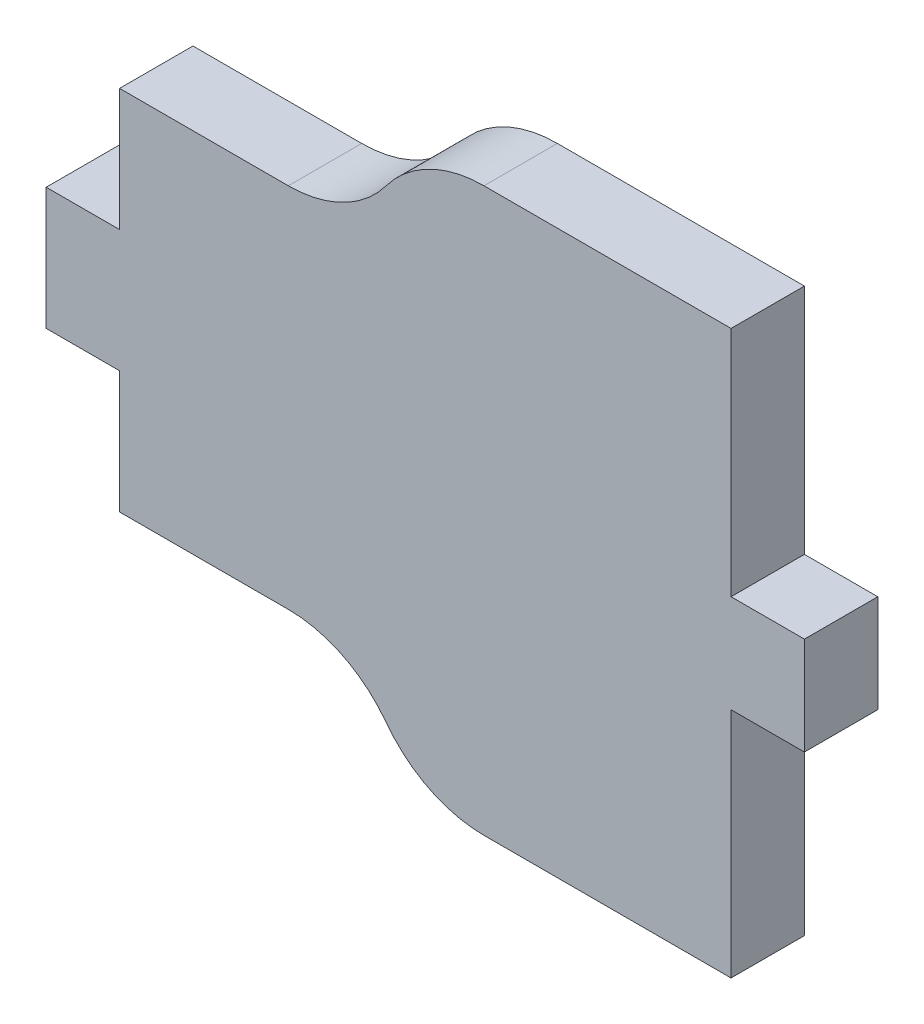
SolidWorks part; units mm, degrees
ref_plane "Plan de face" through (0, 0, 0) normal (0, 0, 1) x (1, 0, 0)
ref_plane "Plan de dessus" through (0, 0, 0) normal (0, 1, 0) x (1, 0, 0)
ref_plane "Plan de droite" through (0, 0, 0) normal (1, 0, 0) x (0, 0, -1)
sketch "Esquisse1" plane through (0, 0, 0) normal (0, 0, 1) x (1, 0, 0)
  line L1 (-22.2671, 18.0667) -> (27.7329, 18.0667)
  line L2 (-22.2671, 18.0667) -> (-22.2671, -11.9333)
  line L3 (-22.2671, -11.9333) -> (27.7329, -11.9333)
  line L4 (27.7329, 18.0667) -> (27.7329, -11.9333)
  dimension "D1" = 50
  dimension "D2" = 30
extrude "Boss.-Extru.1" add sketch "Esquisse1" along normal blind 6
sketch "Esquisse3" plane through (0, 0, 6) normal (0, 0, 1) x (1, 0, 0)
  line L0 (-2.2671, 18.0667) -> (-2.2671, -11.9333) construction
  line L1 (27.7329, 18.0667) -> (-22.2671, 18.0667) construction
  line L2 (-22.2671, -11.9333) -> (27.7329, -11.9333) construction
  line L3 (27.7329, -11.9333) -> (27.7329, 18.0667) construction
  line L5 (-2.2671, 18.0667) -> (27.7329, 18.0667)
  line L6 (-2.2671, 18.0667) -> (-2.2671, 26.0667)
  line L7 (-2.2671, 26.0667) -> (27.7329, 26.0667)
  line L8 (27.7329, 18.0667) -> (27.7329, 26.0667)
  line L9 (-2.2671, -11.9333) -> (27.7329, -11.9333)
  line L10 (-2.2671, -11.9333) -> (-2.2671, -19.9333)
  line L11 (-2.2671, -19.9333) -> (27.7329, -19.9333)
  line L12 (27.7329, -11.9333) -> (27.7329, -19.9333)
  dimension "D1" = 30
  dimension "D2" = 30
  dimension "D3" = 8
  dimension "D4" = 8
  dimension "D5" = 30
extrude "Boss.-Extru.2" add sketch "Esquisse3" against normal blind 6
fillet "Congé1" radius 10 1 edges at (-2.2671, 26.0667, 3)
fillet "Congé2" radius 10 1 edges at (-2.2671, -19.9333, 3)
fillet "Congé3" radius 10 1 edges
fillet "Congé4" radius 10 1 edges
sketch "Esquisse7" plane through (0, 0, 6) normal (0, 0, 1) x (1, 0, 0)
  line L0 (-22.2671, 18.0667) -> (-22.2671, -11.9333) construction
  line L1 (-22.2671, 8.0667) -> (-28.2671, 8.0667)
  line L2 (-22.2671, 8.0667) -> (-22.2671, -1.9333)
  line L3 (-22.2671, -1.9333) -> (-28.2671, -1.9333)
  line L4 (-28.2671, 8.0667) -> (-28.2671, -1.9333)
  line L5 (-8.4691, 18.0667) -> (-22.2671, 18.0667) construction
  line L6 (-22.2671, -11.9333) -> (-8.4691, -11.9333) construction
  line L7 (27.7329, -19.9333) -> (27.7329, 26.0667) construction
  line L8 (27.7329, 7.0667) -> (33.7329, 7.0667)
  line L9 (27.7329, 7.0667) -> (27.7329, -0.9333)
  line L10 (27.7329, -0.9333) -> (33.7329, -0.9333)
  line L11 (33.7329, 7.0667) -> (33.7329, -0.9333)
  line L12 (27.7329, 26.0667) -> (7.5309, 26.0667) construction
  line L13 (7.5309, -19.9333) -> (27.7329, -19.9333) construction
  dimension "D1" = 6
  dimension "D2" = 10
  dimension "D3" = 10
  dimension "D4" = 10
  dimension "D5" = 6
  dimension "D6" = 19
  dimension "D7" = 19
extrude "Boss.-Extru.3" add sketch "Esquisse7" against normal blind 6
